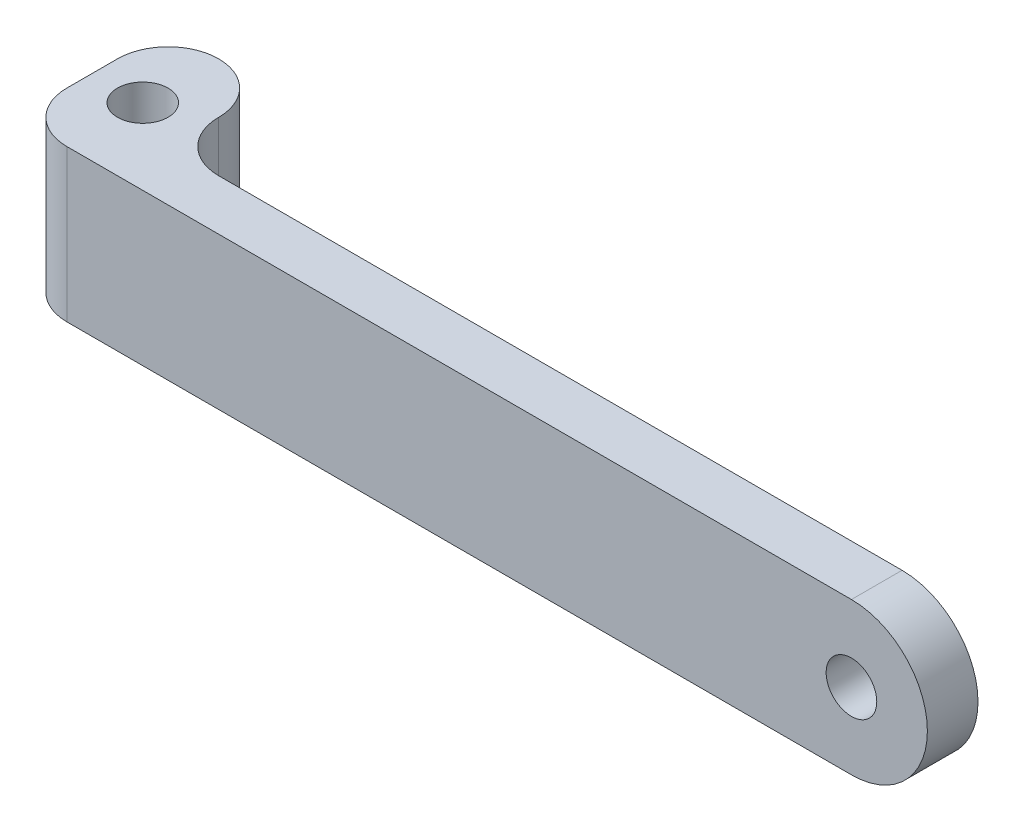
SolidWorks part; units mm, degrees
ref_plane "Front Plane" through (0, 0, 0) normal (0, 0, 1) x (1, 0, 0)
ref_plane "Top Plane" through (0, 0, 0) normal (0, 1, 0) x (1, 0, 0)
ref_plane "Right Plane" through (0, 0, 0) normal (1, 0, 0) x (0, 0, -1)
sketch "Sketch1" plane through (0, 0, 0) normal (0, 0, 1) x (1, 0, 0)
  line L0 (0, 0) -> (75, 0) construction
  line L1 (0, 7.5) -> (75, 7.5)
  line L2 (0, -7.5) -> (75, -7.5)
  line L3 (37.5, 0) -> (37.5, 9.1494) construction
  line L4 (0, 7.5) -> (75, 7.5) construction
  circle A0 centre (0, 0) radius 7.5
  circle A1 centre (0, 0) radius 2.5
  circle A2 centre (75, 0) radius 7.5
  circle A3 centre (75, 0) radius 2.5
  dimension "D2" = 5
  dimension "D3" = 15
  dimension "D4" = 15
  dimension "D5" = 5
  dimension "D1" = 75
  dimension "D6" = 90
extrude "Boss-Extrude1" add sketch "Sketch1" along normal blind 5 contours A0 A1 | A2 L1 A0 L2 | A2 A3 region at (37.5, 0, 0) region at (5.1533, 5.1533, 0) region at (80.1533, 5.1533, 0)
sketch "Sketch3" plane through (0, 7.5, 0) normal (0, 1, 0) x (1, 0, 0)
  line L1 (-7.5, -5) -> (2.5, -5)
  line L2 (-7.5, -5) -> (-7.5, 10)
  line L3 (-7.5, 10) -> (2.5, 10)
  line L4 (2.5, -5) -> (2.5, 10)
  dimension "D1" = 10
  dimension "D2" = 15
extrude "Boss-Extrude2" add sketch "Sketch3" against normal blind 15
sketch "Sketch4" plane through (0, 7.5, 0) normal (0, 1, 0) x (1, 0, 0)
  line L0 (-2.5, 10) -> (-2.5, 2.5) construction
  line L1 (2.5, 10) -> (-7.5, 10) construction
  line L2 (-2.5, 2.5) -> (-2.5, -5) construction
  line L3 (-7.5, -5) -> (75, -5) construction
  line L4 (2.5, 0) -> (-7.5, 0) construction
  line L5 (-7.5, 10) -> (-7.5, -5) construction
  circle A0 centre (-2.5, 2.5) radius 2.5
  dimension "D1" = 5
  dimension "D2" = 7.5
extrude "Cut-Extrude1" cut sketch "Sketch4" against normal blind 15
fillet "Fillet1" radius 5 4 edges at (-7.5, 0, 5) (2.5, 0, 0) (2.5, 0, -10) (-7.5, 0, -10)
